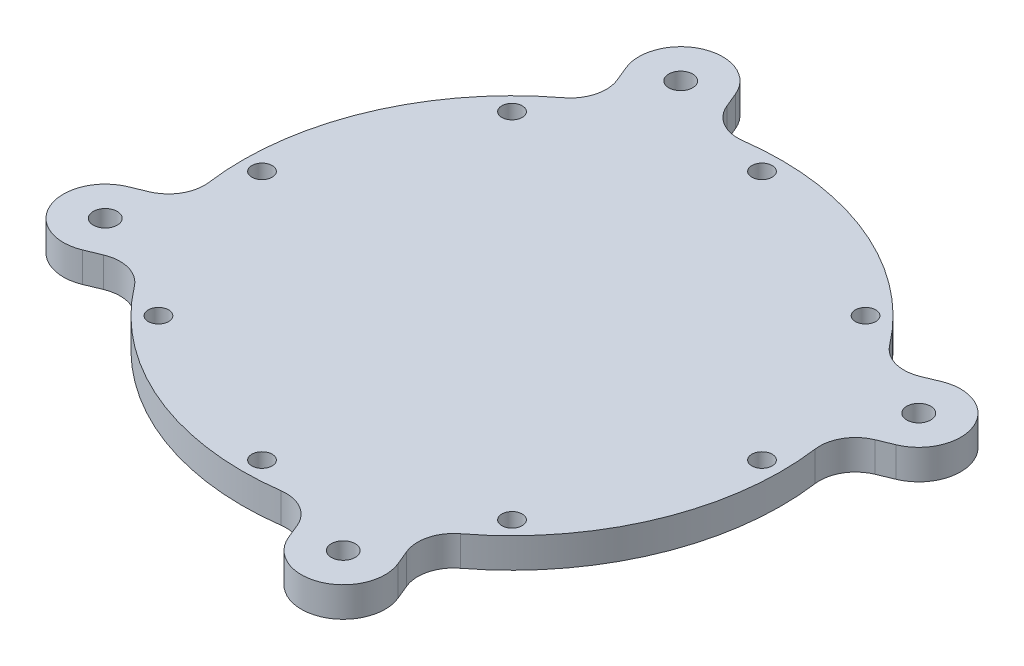
SolidWorks part; units mm, degrees
material "6061-T6 (SS)"
ref_plane "Front Plane" through (0, 0, 0) normal (0, 0, 1) x (1, 0, 0)
ref_plane "Top Plane" through (0, 0, 0) normal (0, 1, 0) x (1, 0, 0)
ref_plane "Right Plane" through (0, 0, 0) normal (1, 0, 0) x (0, 0, -1)
sketch "Sketch1" plane through (0, 0, 0) normal (0, 1, 0) x (1, 0, 0)
  circle A0 centre (0, 0) radius 45
  circle A1 centre (0, 41.75) radius 1.5
  circle A2 centre (29.5217, 29.5217) radius 1.5
  circle A3 centre (41.75, 0) radius 1.5
  circle A4 centre (29.5217, -29.5217) radius 1.5
  circle A5 centre (0, -41.75) radius 1.5
  circle A6 centre (-29.5217, -29.5217) radius 1.5
  circle A7 centre (-41.75, 0) radius 1.5
  circle A8 centre (-29.5217, 29.5217) radius 1.5
  point P22 (0, 0)
  dimension "D1" = 8
extrude "Boss-Extrude2" add sketch "Sketch1" along normal blind 5
sketch "Sketch9" plane through (0, 0, 0) normal (0, -1, 0) x (1, 0, 0)
  circle A2 centre (27, 0) radius 3.937
  circle A3 centre (0, -27) radius 3.937
  circle A4 centre (-27, 0) radius 3.937
  circle A5 centre (0, 27) radius 3.937
  point P15 (0, 0)
  dimension "D1" = 4
extrude "Boss-Extrude7" add sketch "Sketch9" along normal blind 4
sketch "Sketch10" plane through (0, 5, 0) normal (0, 1, 0) x (1, 0, 0)
  circle A0 centre (0, 41.75) radius 1.7
  circle A1 centre (29.5217, 29.5217) radius 1.7
  circle A2 centre (41.75, 0) radius 1.7
  circle A3 centre (29.5217, -29.5217) radius 1.7
  circle A4 centre (0, -41.75) radius 1.7
  circle A5 centre (-29.5217, -29.5217) radius 1.7
  circle A6 centre (-41.75, 0) radius 1.7
  circle A7 centre (-29.5217, 29.5217) radius 1.7
  point P19 (0, 0)
  dimension "D1" = 8
extrude "Cut-Extrude9" cut sketch "Sketch10" against normal blind 14
sketch "Sketch16" plane through (0, 0, 0) normal (0, -1, 0) x (1, 0, 0)
  line L0 (0, 0) -> (45, 0)
  line L1 (0, 0) -> (41.5746, 17.2208)
  line L2 (-58.808, 24.3233) -> (24.3233, 58.808)
  line L3 (-58.808, 24.3233) -> (-24.3233, -58.808)
  line L4 (24.3233, 58.808) -> (58.808, -24.3233)
  line L5 (-24.3233, -58.808) -> (58.808, -24.3233)
  line L6 (-58.808, 24.3233) -> (58.808, -24.3233) construction
  line L7 (24.3233, 58.808) -> (-24.3233, -58.808) construction
  line L8 (0, 0) -> (48.0521, -19.8746)
  line L9 (48.0521, -19.8746) -> (50.7275, -13.406)
  line L10 (50.7275, -13.406) -> (45.3766, -26.3431)
  line L11 (54.6528, -30.1798) -> (60.0037, -17.2427)
  line L12 (54.6528, -30.1798) -> (36.1004, -22.5065)
  line L13 (60.0037, -17.2427) -> (41.4513, -9.5694)
  line L14 (36.1004, -22.5065) -> (41.4513, -9.5694)
  line L15 (54.6528, -30.1798) -> (41.4513, -9.5694) construction
  line L16 (60.0037, -17.2427) -> (36.1004, -22.5065) construction
  circle A0 centre (0, 0) radius 45 construction
  circle A1 centre (48.0521, -19.8746) radius 7
  circle A2 centre (48.0521, -19.8746) radius 2
  dimension "D1" = 22.5
  dimension "D2" = 90
  dimension "D3" = 90
  dimension "D4" = 52
extrude "Boss-Extrude8" add sketch "Sketch16" against normal up to surface (5 mm away) contours A1 L12 | A1 L13 | A2 L8 A1 L10 | A2 L10 A1 L8 | A2 L10 A1 region at (42.7047, 0, -13.1821) region at (39.5396, 0, -20.8346) region at (46.34, 0, -15.7474) region at (43.9248, 0, -21.5867) region at (50.9717, 0, -21.0822) up to face at (0, 5, -40.05)
fillet "Fillet1" radius 6 2 edges at (43.7528, 2.5, -10.5213) (38.4019, 2.5, -23.4584)
sketch "Sketch17" plane through (0, 5, 0) normal (0, 1, 0) x (1, 0, 0)
  circle A0 centre (0, 0) radius 8.3177
extrude "Boss-Extrude9" add sketch "Sketch17" along normal blind 10
pattern_circular "CirPattern1" count 4 over 360 about axis through (0, 15, 0) along (0, 1, 0) of "Boss-Extrude8", "Fillet1"
sketch "Sketch18" plane through (0, 0, 0) normal (0, 0, 1) x (1, 0, 0)
  line L1 (8.3177, 15) -> (-8.3177, 15)
  line L2 (8.3177, 15) -> (8.3177, 5)
  line L3 (8.3177, 5) -> (-8.3177, 5)
  line L4 (-8.3177, 15) -> (-8.3177, 5)
  line L5 (-30.937, 0) -> (30.937, 0)
  line L6 (-30.937, 0) -> (-30.937, -4)
  line L7 (-30.937, -4) -> (30.937, -4)
  line L8 (30.937, 0) -> (30.937, -4)
extrude "Cut-Extrude10" cut sketch "Sketch18" against normal through all both and the other way through all
sketch "Sketch19" plane through (0, 0, 0) normal (0, -1, 0) x (1, 0, 0)
  circle A1 centre (-18.4816, 7.6441) radius 1.5
  circle A2 centre (7.6441, 18.4816) radius 1.5
  circle A3 centre (18.4816, -7.6441) radius 1.5
  circle A4 centre (-7.6441, -18.4816) radius 1.5
  point P18 (0, 0)
  dimension "D2" = 4
hole_wizard "M3x0.5 Tapped Hole1" positions "Sketch23" profile "Sketch24" tap size "M3x0.5" standard "ANSI Metric"
sketch "Sketch23" plane through (0, 0, 0) normal (0, -1, 0) x (-1, 0, 0)
  point P0 (-18.4816, 7.6441)
  point P3 (7.6441, 18.4816)
  point P6 (18.4816, -7.6441)
  point P9 (-7.6441, -18.4816)
cosmetic thread "Hole Thread1" parameters "D1"=6, "D2"=3
cosmetic thread "Hole Thread2" parameters "D1"=6, "D2"=3
cosmetic thread "Hole Thread3" parameters "D1"=6, "D2"=3
cosmetic thread "Hole Thread4" parameters "D1"=6, "D2"=3
sketch "Sketch24" plane through (18.4816, 0, -7.6441) normal (1, 0, 0) x (0, 0, -1)
  line L0 (0, 0) -> (0, 4)
  line L1 (0, 4) -> (1.25, 3.2489)
  line L2 (1.25, 3.2489) -> (1.25, 0.275)
  line L3 (1.25, 0.275) -> (1.525, 0)
  line L5 (1.525, 0) -> (0, 0)
  line L6 (-1.25, 0.275) -> (-1.525, 0) construction
  line L10 (0, 4) -> (-1.25, 3.2489) construction
  line L11 (0, -6.35) -> (0, 107.95) construction
  dimension "Tap Drill Dia." = 2.5
  dimension "Tap Drill Depth" = 4
  dimension "Near C'Sink Dia." = 3.05
  dimension "Near C'Sink Angle" = 90
  dimension "Drill Angle" = 118
